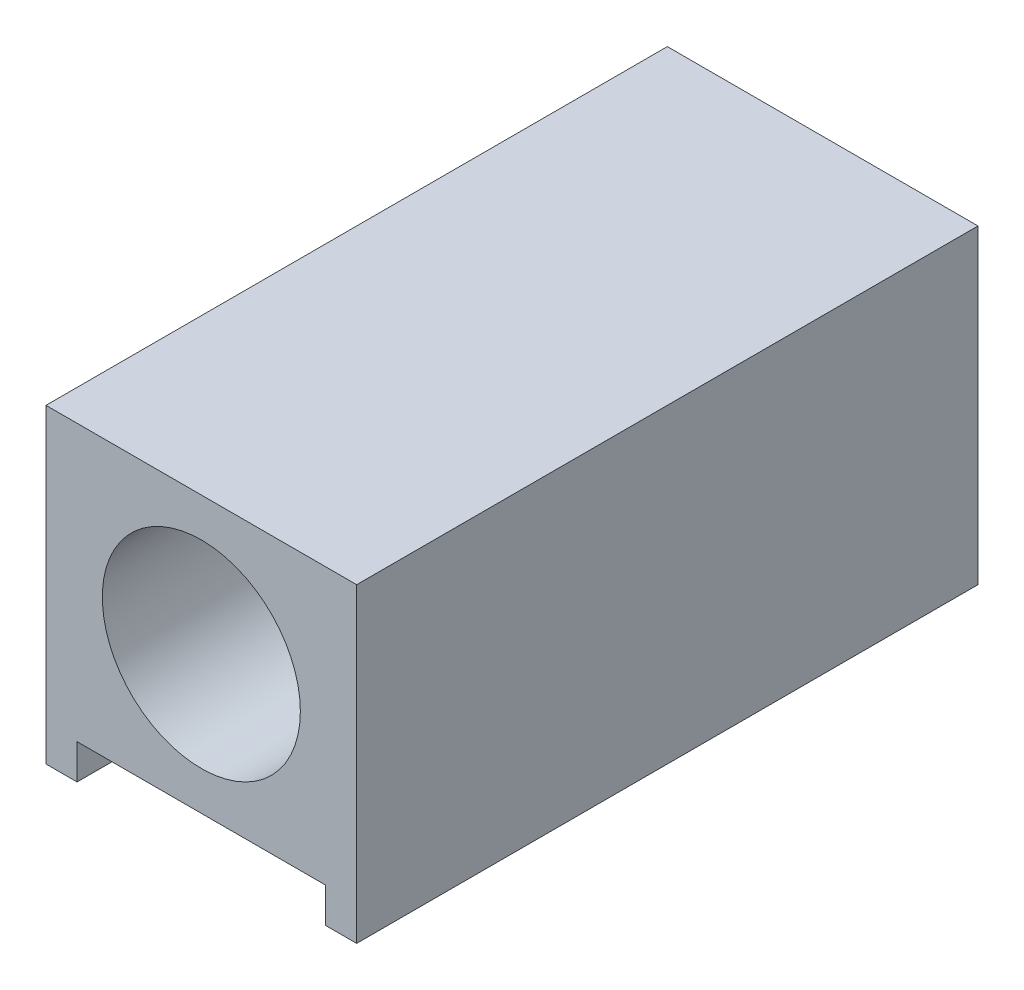
SolidWorks part; units mm, degrees
ref_plane "Front Plane" through (0, 0, 0) normal (0, 0, 1) x (1, 0, 0)
ref_plane "Top Plane" through (0, 0, 0) normal (0, 1, 0) x (1, 0, 0)
ref_plane "Right Plane" through (0, 0, 0) normal (1, 0, 0) x (0, 0, -1)
sketch "Sketch1" plane through (0, 0, 0) normal (0, 1, 0) x (1, 0, 0)
  line L1 (-10.5609, 19.2861) -> (5.4391, 19.2861)
  line L2 (-10.5609, 19.2861) -> (-10.5609, -12.7139)
  line L3 (-10.5609, -12.7139) -> (5.4391, -12.7139)
  line L4 (5.4391, 19.2861) -> (5.4391, -12.7139)
  dimension "D1" = 16
  dimension "D2" = 32
extrude "Boss-Extrude1" add sketch "Sketch1" along normal blind 14.2
sketch "Sketch3" plane through (0, 0, 0) normal (0, -1, 0) x (1, 0, 0)
  line L0 (-10.5609, 12.7139) -> (5.4391, 12.7139) construction
  line L1 (-10.5609, -19.2861) -> (-8.9609, -19.2861)
  line L2 (-10.5609, -19.2861) -> (-10.5609, 12.7139)
  line L3 (-10.5609, 12.7139) -> (-8.9609, 12.7139)
  line L4 (-8.9609, -19.2861) -> (-8.9609, 12.7139)
  line L6 (5.4391, -19.2861) -> (3.8391, -19.2861)
  line L7 (5.4391, -19.2861) -> (5.4391, 12.7139)
  line L8 (5.4391, 12.7139) -> (3.8391, 12.7139)
  line L9 (3.8391, -19.2861) -> (3.8391, 12.7139)
  dimension "D1" = 1.6
  dimension "D2" = 1.6
extrude "Boss-Extrude2" add sketch "Sketch3" along normal blind 1.8
sketch "Sketch4" plane through (0, 0, 12.7139) normal (0, 0, 1) x (1, 0, 0)
  line L0 (5.4391, 14.2) -> (5.4391, -1.8) construction
  line L2 (-8.9609, 0) -> (3.8391, 0) construction
  circle A0 centre (-2.5609, 7.1) radius 5.1
  dimension "D1" = 10.2
  dimension "D2" = 8
  dimension "D3" = 7.1
extrude "Cut-Extrude1" cut sketch "Sketch4" against normal through all
sketch "Sketch5" plane through (0, 0, 0) normal (0, -1, 0) x (1, 0, 0)
  line L1 (3.8391, -19.2861) -> (-1.5609, -19.2861)
  line L2 (3.8391, -19.2861) -> (3.8391, -17.6861)
  line L3 (3.8391, -17.6861) -> (-1.5609, -17.6861)
  line L4 (-1.5609, -19.2861) -> (-1.5609, -17.6861)
  line L5 (-8.9609, -19.2861) -> (-3.5609, -19.2861)
  line L6 (-8.9609, -19.2861) -> (-8.9609, -17.6861)
  line L7 (-8.9609, -17.6861) -> (-3.5609, -17.6861)
  line L8 (-3.5609, -19.2861) -> (-3.5609, -17.6861)
  dimension "D1" = 1.6
  dimension "D2" = 1.6
  dimension "D3" = 2
  dimension "D4" = 5.4
  dimension "D5" = 5.4
extrude "Boss-Extrude3" add sketch "Sketch5" against normal blind 13
fillet "Fillet1" radius 1 4 edges at (-3.5609, 12.101, -18.4861) (-1.5609, 12.101, -18.4861) (-3.5609, 2.099, -18.4861) (-1.5609, 2.099, -18.4861)
